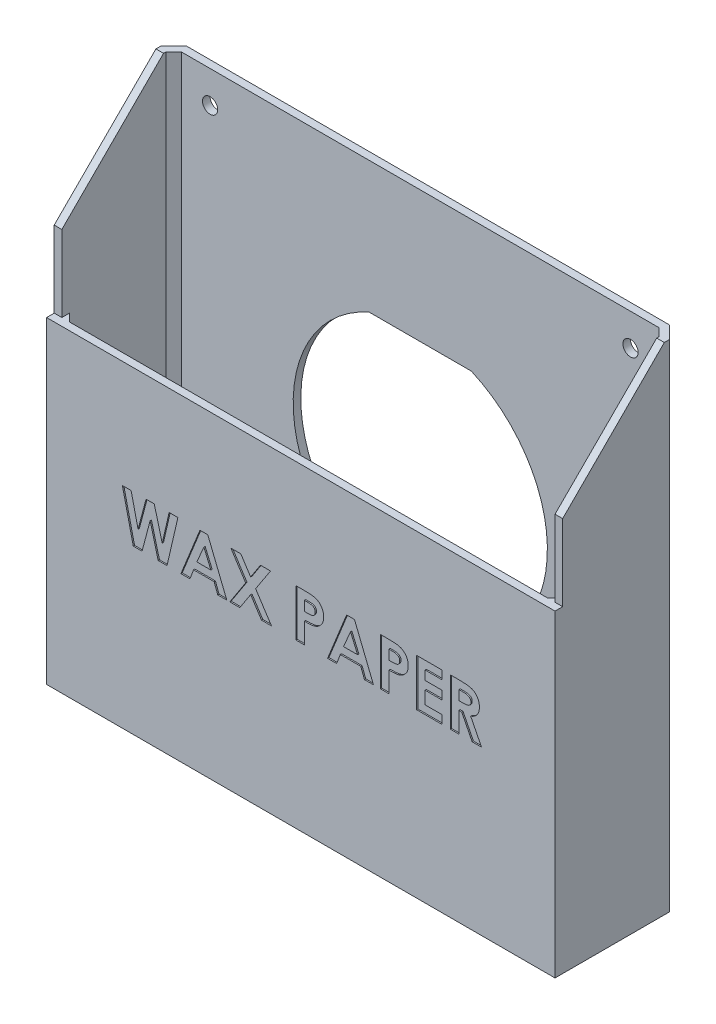
SolidWorks part; units mm, degrees
ref_plane "Front Plane" through (0, 0, 0) normal (0, 0, 1) x (1, 0, 0)
ref_plane "Top Plane" through (0, 0, 0) normal (0, 1, 0) x (1, 0, 0)
ref_plane "Right Plane" through (0, 0, 0) normal (1, 0, 0) x (0, 0, -1)
sketch "Sketch1" plane through (0, 0, 0) normal (0, 1, 0) x (1, 0, 0)
  line L1 (-100, -25) -> (100, -25)
  line L2 (-100, -25) -> (-100, 25)
  line L3 (-100, 25) -> (100, 25)
  line L4 (100, -25) -> (100, 25)
  line L5 (-100, -25) -> (100, 25) construction
  line L6 (-100, 25) -> (100, -25) construction
  point P0 (0, 0)
  dimension "D1" = 200
  dimension "D2" = 50
extrude "Boss-Extrude1" add sketch "Sketch1" along normal blind 5
sketch "Sketch2" plane through (0, 5, 0) normal (0, 1, 0) x (1, 0, 0)
  line L0 (-97, 24.25) -> (-97, 22) construction
  line L1 (-100, -25) -> (100, -25)
  line L2 (-100, -25) -> (-100, 25)
  line L3 (-100, 25) -> (100, 25)
  line L4 (100, -25) -> (100, 25)
  line L5 (-100, -25) -> (100, 25) construction
  line L6 (-100, 25) -> (100, -25) construction
  line L7 (-100, 25) -> (-97, 25)
  line L8 (-100, 25) -> (-100, 22)
  line L9 (-100, 22) -> (-97, 22) construction
  line L10 (-97, 25) -> (-97, 24.25) construction
  line L11 (97, -22) -> (-97, -22)
  line L12 (97, -22) -> (97, 22)
  line L13 (97, 22) -> (-97, 22)
  line L14 (-97, -22) -> (-97, 22)
  line L15 (97, -22) -> (-97, 22) construction
  line L16 (97, 22) -> (-97, -22) construction
  point P0 (0, 0)
  point P10 (0, 0)
  line M1 (100, -25) -> (100, 25)
  line M2 (100, 25) -> (-100, 25)
  line M3 (-100, 25) -> (-100, -25)
  line M4 (-100, -25) -> (100, -25)
extrude "Boss-Extrude2" add sketch "Sketch2" along normal blind 120 contours L3 L2 L11 L14 L13 L12 M4 M1 M2 M3 region at (-97.9384, 5, 1.5)
sketch "Sketch3" plane through (0, 125, 0) normal (0, 1, 0) x (1, 0, 0)
  line L0 (100, -25) -> (100, 25) construction
  line L1 (-100, 25) -> (100, 25)
  line L2 (-100, 25) -> (-100, 22)
  line L3 (-97, 22) -> (97, 22)
  line L4 (100, 25) -> (100, 22)
  line L5 (-100, 22) -> (-97, 22) construction
  line L6 (-97, -22) -> (-100, -22)
  line L7 (-97, -22) -> (-97, 22)
  line L8 (-97, 22) -> (-100, 22) construction
  line L9 (-100, -22) -> (-100, 22)
  line L10 (97, -22) -> (100, -22)
  line L11 (97, -22) -> (97, 22)
  line L12 (97, 22) -> (100, 22) construction
  line L13 (100, -22) -> (100, 22)
  line L14 (97, 22) -> (100, 22) construction
extrude "Boss-Extrude3" add sketch "Sketch3" along normal blind 70
chamfer "Chamfer1" distance 40 angle 45 2 edges at (98.5, 195, 22) (-98.5, 195, 22)
chamfer "Chamfer2" distance 5 angle 45 4 edges at (-97, 5, 0) (0, 5, -22) (97, 5, 0) (0, 5, 22)
chamfer "Chamfer3" distance 3 angle 45 4 edges at (-97, 67.5, 22) (97, 67.5, 22) (97, 102.5, -22) (-97, 102.5, -22)
chamfer "Chamfer4" distance 5 angle 45 2 edges at (100, 97.5, -25) (-100, 97.5, -25)
sketch "Sketch4" plane through (0, 0, -25) normal (0, 0, -1) x (-1, 0, 0)
  line L0 (-95, 97.5) -> (-50, 97.5) construction
  line L1 (-95, 195) -> (-95, 0) construction
  line L2 (95, 0) -> (95, 195) construction
  line L3 (-50, 97.5) -> (50, 97.5) construction
  line L4 (50, 97.5) -> (95, 97.5) construction
  line L5 (-13.5694, 145.6235) -> (13.5694, 145.6235) construction
  line L6 (-20.0975, 143.2831) -> (20.0975, 143.2831)
  line L7 (-95, 182.4076) -> (-85.6874, 182.4076) construction
  line L8 (-82.6874, 182.4076) -> (-79.6874, 182.4076) construction
  line L9 (-79.6874, 182.4076) -> (79.6874, 182.4076) construction
  line L10 (82.6874, 182.4076) -> (85.6874, 182.4076) construction
  line L11 (-79.6874, 182.4076) -> (79.6874, 182.4076) construction
  line L12 (79.6874, 182.4076) -> (82.6874, 182.4076) construction
  line L13 (-82.6874, 182.4076) -> (-79.6874, 182.4076) construction
  line L14 (-85.6874, 182.4076) -> (-82.6874, 182.4076) construction
  line L15 (85.6874, 182.4076) -> (95, 182.4076) construction
  line L16 (79.6874, 182.4076) -> (82.6874, 182.4076) construction
  arc A0 (-20.0975, 143.2831) -> (20.0975, 143.2831) centre (0, 97.5) ccw
  arc A1 (13.5694, 145.6235) -> (-13.5694, 145.6235) centre (0, 97.5) ccw construction
  arc A2 (-13.5694, 145.6235) -> (-20.0975, 143.2831) centre (0, 97.5) ccw construction
  arc A3 (20.0975, 143.2831) -> (13.5694, 145.6235) centre (0, 97.5) ccw construction
  circle A4 centre (-82.6874, 182.4076) radius 3
  circle A5 centre (82.6874, 182.4076) radius 3
  point P18 (0, 182.4076)
extrude "Cut-Extrude1" cut sketch "Sketch4" against normal up to surface (3 mm away) up to face at (0, 102.5, -22)
sketch "Sketch5" plane through (0, 0, 25) normal (0, 0, 1) x (1, 0, 0)
  text T0 "<b>WAX PAPER</b>\r\n\r\n" font "Century Gothic" height in points 70
extrude "Cut-Extrude2" cut sketch "Sketch5" against normal blind 0.5
